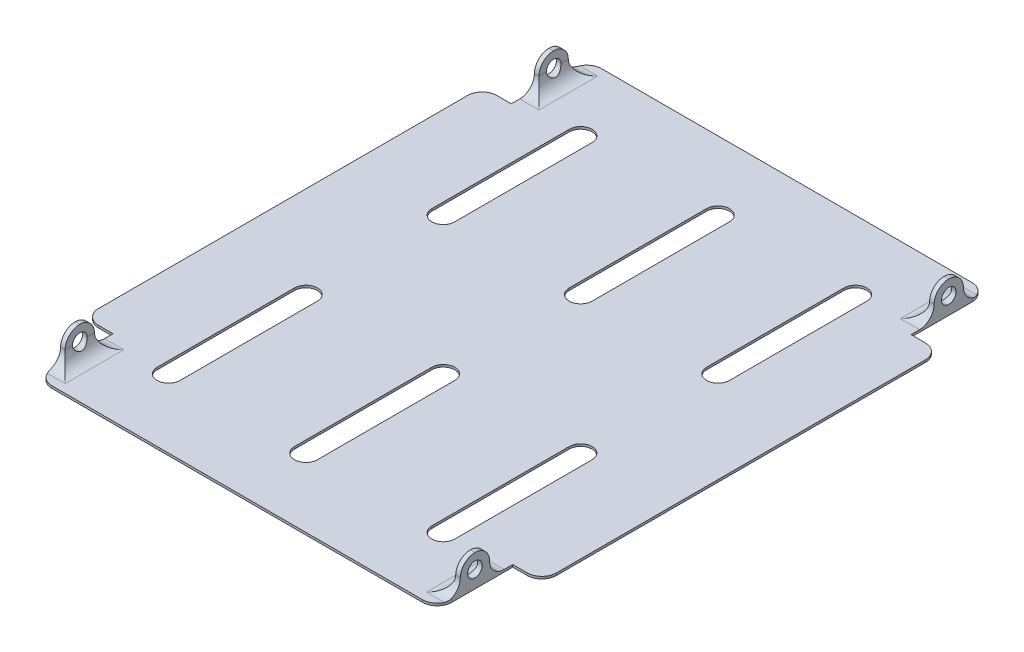
SolidWorks part; units mm, degrees
material "C355.0-T61 Permanent Mold cast (SS)"
ref_plane "Front Plane" through (0, 0, 0) normal (0, 0, 1) x (1, 0, 0)
ref_plane "Top Plane" through (0, 0, 0) normal (0, 1, 0) x (1, 0, 0)
ref_plane "Right Plane" through (0, 0, 0) normal (1, 0, 0) x (0, 0, -1)
sketch "Sketch1" plane through (0, 0, 0) normal (0, 1, 0) x (1, 0, 0)
  line L1 (-500, -600) -> (500, -600)
  line L2 (-500, -600) -> (-500, 600)
  line L3 (-500, 600) -> (500, 600)
  line L4 (500, -600) -> (500, 600)
  line L5 (-500, -600) -> (500, 600) construction
  line L6 (-500, 600) -> (500, -600) construction
  line L7 (-500, -600) -> (-436.5, -600)
  line L8 (-500, -600) -> (-500, -434.9)
  line L9 (-500, -434.9) -> (-436.5, -434.9)
  line L10 (-436.5, -600) -> (-436.5, -434.9)
  line L11 (500, -600) -> (436.5, -600)
  line L12 (500, -600) -> (500, -434.9)
  line L13 (500, -434.9) -> (436.5, -434.9)
  line L14 (436.5, -600) -> (436.5, -434.9)
  line L15 (-500, 600) -> (-436.5, 600)
  line L16 (-500, 600) -> (-500, 434.9)
  line L17 (-500, 434.9) -> (-436.5, 434.9)
  line L18 (-436.5, 600) -> (-436.5, 434.9)
  line L19 (500, 600) -> (436.5, 600)
  line L20 (500, 600) -> (500, 434.9)
  line L21 (500, 434.9) -> (436.5, 434.9)
  line L22 (436.5, 600) -> (436.5, 434.9)
  point P0 (0, 0)
  dimension "D1" = 1200
  dimension "D2" = 1000
  dimension "D3" = 165.1
  dimension "D4" = 63.5
extrude "Boss-Extrude1" add sketch "Sketch1" along normal blind 5 contours L22 L3 L18 L17 L2 L9 L10 L1 L14 L13 L4 L21 region at (0, 0, 0)
sketch "Sketch2" plane through (0, 5, 0) normal (0, 1, 0) x (1, 0, 0)
  line L0 (0, -300) -> (0, 300) construction
  line L1 (300, 0) -> (-300, 0) construction
  line L2 (-300, -300) -> (-300, 300) construction
  line L3 (300, -300) -> (300, 300) construction
  line L4 (-300, -150) -> (-300, -450) construction
  line L5 (-275, -150) -> (-275, -450)
  line L6 (-325, -150) -> (-325, -450)
  line L7 (-300, 150) -> (-300, 450) construction
  line L8 (-325, 150) -> (-325, 450)
  line L9 (-275, 150) -> (-275, 450)
  line L10 (0, 150) -> (0, 450) construction
  line L11 (-25, 150) -> (-25, 450)
  line L12 (25, 150) -> (25, 450)
  line L13 (0, -150) -> (0, -450) construction
  line L14 (25, -150) -> (25, -450)
  line L15 (-25, -150) -> (-25, -450)
  line L16 (300, 150) -> (300, 450) construction
  line L17 (275, 150) -> (275, 450)
  line L18 (325, 150) -> (325, 450)
  line L19 (300, -150) -> (300, -450) construction
  line L20 (325, -150) -> (325, -450)
  line L21 (275, -150) -> (275, -450)
  arc A0 (-275, -150) -> (-325, -150) centre (-300, -150) ccw
  arc A1 (-325, -450) -> (-275, -450) centre (-300, -450) ccw
  arc A2 (-325, 150) -> (-275, 150) centre (-300, 150) ccw
  arc A3 (-275, 450) -> (-325, 450) centre (-300, 450) ccw
  arc A4 (-25, 150) -> (25, 150) centre (0, 150) ccw
  arc A5 (25, 450) -> (-25, 450) centre (0, 450) ccw
  arc A6 (25, -150) -> (-25, -150) centre (0, -150) ccw
  arc A7 (-25, -450) -> (25, -450) centre (0, -450) ccw
  arc A8 (275, 150) -> (325, 150) centre (300, 150) ccw
  arc A9 (325, 450) -> (275, 450) centre (300, 450) ccw
  arc A10 (325, -150) -> (275, -150) centre (300, -150) ccw
  arc A11 (275, -450) -> (325, -450) centre (300, -450) ccw
  point P4 (0, 0)
  point P8 (0, 0)
  point P11 (-300, 0)
  point P14 (300, 0)
  point P16 (-300, -300)
  point P22 (-300, 300)
  point P30 (0, 300)
  point P36 (0, -300)
  point P44 (300, 300)
  point P50 (300, -300)
  dimension "D3" = 25
  dimension "D1" = 600
  dimension "D2" = 600
  dimension "D4" = 300
extrude "Cut-Extrude1" cut sketch "Sketch2" against normal up to next
sketch "Sketch3" plane through (436.5, 0, 0) normal (1, 0, 0) x (0, 0, -1)
  line L0 (-517.45, 5) -> (-517.45, 37) construction
  line L1 (-600, 5) -> (-434.9, 5) construction
  line L2 (517.45, 5) -> (517.45, 37) construction
  line L3 (600, 5) -> (434.9, 5) construction
  line L5 (-549.45, 69) -> (-485.45, 69)
  line L6 (-549.45, 69) -> (-549.45, 5)
  line L7 (-549.45, 5) -> (-485.45, 5)
  line L8 (-485.45, 69) -> (-485.45, 5)
  line L9 (-549.45, 69) -> (-485.45, 5) construction
  line L10 (-549.45, 5) -> (-485.45, 69) construction
  line L11 (485.45, 69) -> (549.45, 69)
  line L12 (485.45, 69) -> (485.45, 5)
  line L13 (485.45, 5) -> (549.45, 5)
  line L14 (549.45, 69) -> (549.45, 5)
  line L15 (485.45, 69) -> (549.45, 5) construction
  line L16 (485.45, 5) -> (549.45, 69) construction
  circle A0 centre (-517.45, 37) radius 16
  circle A1 centre (517.45, 37) radius 16
  dimension "D2" = 32
  dimension "D1" = 32
extrude "Boss-Extrude2" add sketch "Sketch3" against normal blind 10
fillet "Fillet1" radius 32 10 edges at (431.5, 69, -485.45) (431.5, 5, -485.45) (431.5, 5, -549.45) (431.5, 69, -549.45) (431.5, 69, 549.45) (431.5, 69, 485.45) (431.5, 5, 485.45) (431.5, 5, 549.45) (426.5, 5, 517.45) (426.5, 5, -517.45)
mirror "Mirror1" about plane through (0, 0, 0) normal (1, 0, 0) of "Fillet1", "Boss-Extrude2"
fillet "Fillet2" radius 32 8 edges at (436.5, 2.5, 600) (436.5, 2.5, -600) (-436.5, 2.5, -600) (-436.5, 2.5, 600) (-500, 2.5, 434.9) (-500, 2.5, -434.9) (500, 2.5, -434.9) (500, 2.5, 434.9)
